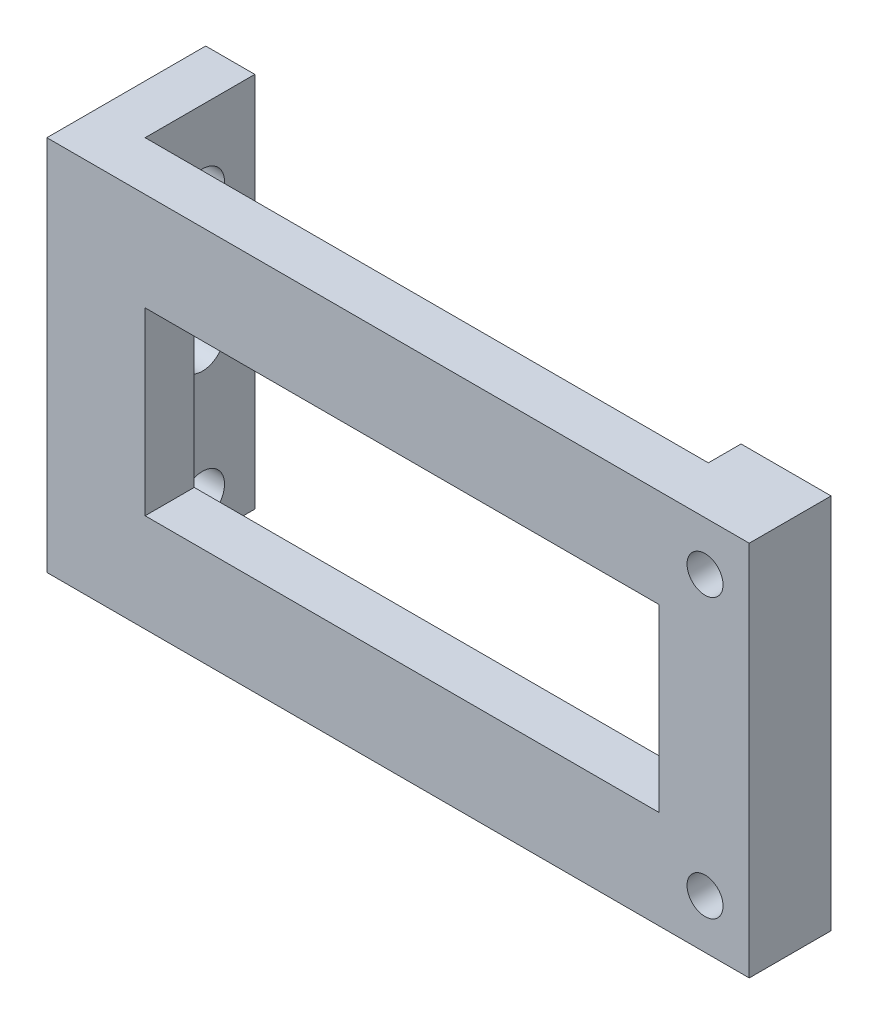
SolidWorks part; units mm, degrees
ref_plane "Front Plane" through (0, 0, 0) normal (0, 0, 1) x (1, 0, 0)
ref_plane "Top Plane" through (0, 0, 0) normal (0, 1, 0) x (1, 0, 0)
ref_plane "Right Plane" through (0, 0, 0) normal (1, 0, 0) x (0, 0, -1)
sketch "Sketch1" plane through (0, 0, 0) normal (0, 0, 1) x (1, 0, 0)
  line L0 (-15.45, 11.5) -> (-15.45, 5.5) construction
  line L1 (21.45, 11.5) -> (-21.45, 11.5)
  line L2 (21.45, 11.5) -> (21.45, -11.5)
  line L3 (21.45, -11.5) -> (-21.45, -11.5)
  line L4 (-21.45, 11.5) -> (-21.45, -11.5)
  line L5 (21.45, 11.5) -> (-21.45, -11.5) construction
  line L6 (21.45, -11.5) -> (-21.45, 11.5) construction
  line L7 (-21.45, 11.5) -> (-18.45, 11.5)
  line L8 (-21.45, 11.5) -> (-21.45, -11.5)
  line L9 (-21.45, -11.5) -> (-18.45, -11.5)
  line L10 (-18.45, 11.5) -> (-18.45, -11.5)
  line L11 (21.45, 11.5) -> (15.95, 11.5)
  line L12 (21.45, 11.5) -> (21.45, -11.5)
  line L13 (21.45, -11.5) -> (15.95, -11.5)
  line L14 (15.95, 11.5) -> (15.95, -11.5)
  line L15 (-15.45, 5.5) -> (15.95, 5.5)
  line L16 (-15.45, 5.5) -> (-15.45, -5.5)
  line L17 (-15.45, -5.5) -> (15.95, -5.5)
  line L18 (15.95, 5.5) -> (15.95, -5.5)
  line L19 (-15.45, 5.5) -> (-21.45, 5.5) construction
  line L20 (-15.45, -5.5) -> (-15.45, -11.5) construction
  circle A0 centre (18.75, -8.5) radius 1.1
  circle A1 centre (18.75, 8.5) radius 1.1
  point P0 (0, 0)
  dimension "D1" = 2.2
  dimension "D2" = 3
  dimension "D3" = 17
  dimension "D4" = 3
  dimension "D5" = 5.5
  dimension "D6" = 2.8
  dimension "D7" = 40.2
  dimension "D8" = 3
  dimension "D9" = 6
extrude "Boss-Extrude1" add sketch "Sketch1" against normal blind 3 contours L14 L1 L10 L3 region at (15.5362, 8.5, 0)
extrude "Boss-Extrude2" add sketch "Sketch1<3>" against normal blind 5 contours L1 L14 L3 L2 A1 A0 region at (18.6968, 0, 0)
sketch "Sketch1<3>" plane through (0, 0, 0) normal (0, 0, 1) x (1, 0, 0) same geometry as "Sketch1"
extrude "Boss-Extrude3" add sketch "Sketch1<4>" against normal blind 9.7 contours L10 L1 L4 L3 region at (-19.95, 0, 0)
sketch "Sketch1<4>" plane through (0, 0, 0) normal (0, 0, 1) x (1, 0, 0) same geometry as "Sketch1"
sketch "Sketch2" plane through (-21.45, 0, 0) normal (-1, 0, 0) x (0, 0, 1)
  line L1 (0, 11.5) -> (0, -11.5) construction
  circle A0 centre (-6.5, 6.75) radius 1.35
  dimension "D1" = 2.7
  dimension "D2" = 1.75
  dimension "D3" = 6.5
extrude "Cut-Extrude1" cut sketch "Sketch2" against normal up to surface (3 mm away) up to face at (-18.45, 0, -6.35)
pattern_linear "LPattern1" count 3 spacing 8 along (0, -1, 0) of "Cut-Extrude1"
